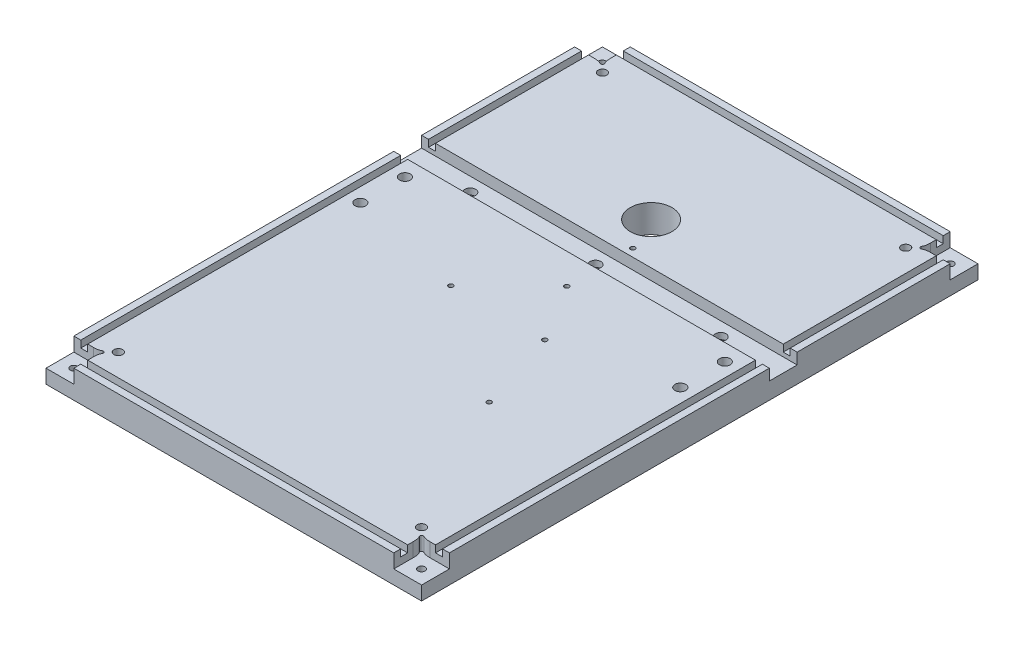
SolidWorks part; units mm, degrees
ref_plane "Front Plane" through (0, 0, 0) normal (0, 0, 1) x (1, 0, 0)
ref_plane "Top Plane" through (0, 0, 0) normal (0, 1, 0) x (1, 0, 0)
ref_plane "Right Plane" through (0, 0, 0) normal (1, 0, 0) x (0, 0, -1)
sketch "Base" plane through (0, 0, 0) normal (0, 1, 0) x (1, 0, 0)
  line L1 (-201.9764, 133.7508) -> (140.9236, 133.7508)
  line L2 (-201.9764, 133.7508) -> (-201.9764, -374.2492)
  line L3 (-201.9764, -374.2492) -> (140.9236, -374.2492)
  line L4 (140.9236, 133.7508) -> (140.9236, -374.2492)
  dimension "D1" = 342.9
  dimension "D2" = 508
extrude "Boss-Extrude1" add sketch "Base" along normal blind 25.4
sketch "Sketch2" plane through (0, 25.4, 0) normal (0, 1, 0) x (1, 0, 0)
  line L1 (172.6736, -31.3492) -> (-233.7264, -31.3492)
  line L2 (172.6736, -31.3492) -> (172.6736, -56.7492)
  line L3 (172.6736, -56.7492) -> (-233.7264, -56.7492)
  line L4 (-233.7264, -31.3492) -> (-233.7264, -56.7492)
  line L6 (140.9236, 133.7508) -> (-201.9764, 133.7508) construction
  line L9 (-30.5264, 133.7508) -> (-30.5264, -374.2492) construction
  line L10 (-201.9764, -374.2492) -> (140.9236, -374.2492) construction
  point P6 (-30.5264, -31.3492)
  dimension "D1" = 317.5
  dimension "D2" = 25.4
  dimension "D3" = 406.4
extrude "Cut-Extrude1" cut sketch "Sketch2" against normal blind 10.16
hole_wizard "CBORE for 3/8 Socket Head Cap Screw4" positions "3DSketch1" profile "Sketch3" counterbore size "3/8" standard "ANSI Inch" end condition up to next
sketch3d "3DSketch1"
  line L3 (-201.9764, 0, -133.7508) -> (-201.9764, 0, 374.2492) construction
  point P0 (83.7736, 0, 44.0492)
  point P2 (-30.5264, 0, 44.0492)
  point P4 (-144.8264, 0, 44.0492)
  dimension "D1" = 12.7
  dimension "D2" = 12.7
  dimension "D3" = 12.7
  dimension "D4" = 171.45
  dimension "D5" = 114.3
  dimension "D6" = 114.3
sketch "Sketch3" plane through (83.7736, 0, 44.0492) normal (1, 0, 0) x (0, 0, -1)
  line L0 (0, 0) -> (0, 15.24)
  line L1 (0, 15.24) -> (4.9022, 15.24)
  line L3 (4.9022, 15.24) -> (4.9022, 9.525)
  line L4 (4.9022, 9.525) -> (7.9375, 9.525)
  line L5 (7.9375, 9.525) -> (7.9375, 0)
  line L7 (7.9375, 0) -> (0, 0)
  line L11 (0, -6.35) -> (0, 107.95) construction
  dimension "Thru Hole Dia." = 9.8044
  dimension "Thru Hole Depth" = 15.24
  dimension "C'Bore Dia." = 15.875
  dimension "C'Bore Depth" = 9.525
hole_wizard "CBORE for 3/8 Socket Head Cap Screw3" positions "Sketch4" profile "Sketch6" counterbore size "3/8" standard "ANSI Inch" end condition up to next
sketch "Sketch4" plane through (0, 0, 0) normal (0, -1, 0) x (-1, 0, 0)
  line L0 (201.9764, -56.7492) -> (-140.9236, -56.7492) construction
  line L1 (-140.9236, -374.2492) -> (-140.9236, 133.7508) construction
  line L3 (201.9764, 133.7508) -> (201.9764, -374.2492) construction
  point P0 (-115.5236, -71.9892)
  point P2 (-115.5236, -112.6292)
  point P4 (176.5764, -71.9892)
  point P6 (176.5764, -112.6292)
  dimension "D1" = 15.24
  dimension "D2" = 25.4
  dimension "D3" = 25.4
  dimension "D4" = 40.64
  dimension "D5" = 15.24
  dimension "D6" = 25.4
  dimension "D7" = 40.64
  dimension "D8" = 25.4
sketch "Sketch6" plane through (115.5236, 0, 71.9892) normal (1, 0, 0) x (0, 0, -1)
  line L0 (0, 0) -> (0, 25.4)
  line L1 (0, 25.4) -> (4.9022, 25.4)
  line L3 (4.9022, 25.4) -> (4.9022, 15.24)
  line L4 (4.9022, 15.24) -> (7.9375, 15.24)
  line L5 (7.9375, 15.24) -> (7.9375, 0)
  line L7 (7.9375, 0) -> (0, 0)
  line L11 (0, -6.35) -> (0, 107.95) construction
  dimension "Thru Hole Dia." = 9.8044
  dimension "Thru Hole Depth" = 25.4
  dimension "C'Bore Dia." = 15.875
  dimension "C'Bore Depth" = 15.24
hole_wizard "CBORE for 1/4 Socket Head Cap Screw1" positions "3DSketch2" profile "Sketch9" counterbore size "1/4" standard "ANSI Inch" end condition up to next
sketch3d "3DSketch2"
  line L0 (140.9236, 0, -133.7508) -> (-201.9764, 0, -133.7508) construction
  line L1 (140.9236, 0, 374.2492) -> (140.9236, 0, -133.7508) construction
  line L2 (-201.9764, 0, -133.7508) -> (-201.9764, 0, 374.2492) construction
  line L3 (-201.9764, 0, 374.2492) -> (140.9236, 0, 374.2492) construction
  point P0 (128.2236, 0, 361.5492)
  point P2 (-189.2764, 0, 361.5492)
  point P4 (-189.2764, 0, -121.0508)
  point P6 (128.2236, 0, -121.0508)
  dimension "D1" = 12.7
  dimension "D2" = 12.7
  dimension "D3" = 12.7
  dimension "D4" = 12.7
  dimension "D5" = 12.7
  dimension "D6" = 12.7
  dimension "D7" = 12.7
  dimension "D8" = 12.7
sketch "Sketch9" plane through (128.2236, 0, 361.5492) normal (1, 0, 0) x (0, 0, -1)
  line L0 (0, 0) -> (0, 25.4)
  line L1 (0, 25.4) -> (3.2639, 25.4)
  line L3 (3.2639, 25.4) -> (3.2639, 6.35)
  line L4 (3.2639, 6.35) -> (5.5562, 6.35)
  line L5 (5.5562, 6.35) -> (5.5562, 0)
  line L7 (5.5562, 0) -> (0, 0)
  line L11 (0, -6.35) -> (0, 107.95) construction
  dimension "Thru Hole Dia." = 6.5278
  dimension "Thru Hole Depth" = 25.4
  dimension "C'Bore Dia." = 11.1125
  dimension "C'Bore Depth" = 6.35
sketch "Sketch8" plane through (0, 25.4, 0) normal (0, 1, 0) x (1, 0, 0)
  line L0 (116.3173, -347.4744) -> (115.5236, -348.8492) construction
  line L1 (140.9236, -374.2492) -> (115.5236, -374.2492)
  line L2 (140.9236, -374.2492) -> (140.9236, -348.8492)
  line L3 (140.9236, -348.8492) -> (123.1436, -348.8492)
  line L4 (115.5236, -374.2492) -> (115.5236, -356.4692)
  line L5 (-201.9764, -374.2492) -> (-176.5764, -374.2492)
  line L6 (-201.9764, -374.2492) -> (-201.9764, -348.8492)
  line L7 (-201.9764, -348.8492) -> (-184.1964, -348.8492)
  line L8 (-176.5764, -374.2492) -> (-176.5764, -356.4692)
  line L9 (-201.9764, 133.7508) -> (-176.5764, 133.7508)
  line L10 (-201.9764, 133.7508) -> (-201.9764, 108.3508)
  line L11 (-201.9764, 108.3508) -> (-184.1964, 108.3508)
  line L12 (-176.5764, 133.7508) -> (-176.5764, 115.9708)
  line L13 (140.9236, 133.7508) -> (115.5236, 133.7508)
  line L14 (140.9236, 133.7508) -> (140.9236, 108.3508)
  line L15 (140.9236, 108.3508) -> (123.1436, 108.3508)
  line L16 (115.5236, 133.7508) -> (115.5236, 115.9708)
  line L17 (115.5236, -348.8492) -> (123.1436, -348.8492) construction
  line L18 (115.5236, -356.4692) -> (115.5236, -348.8492) construction
  line L19 (115.5236, -348.8492) -> (114.1488, -349.6429) construction
  line L20 (115.5236, 108.3508) -> (116.3173, 106.976) construction
  line L21 (115.5236, 108.3508) -> (114.1488, 109.1446) construction
  line L22 (-176.5764, 108.3508) -> (-175.2016, 109.1446) construction
  line L23 (-176.5764, 108.3508) -> (-177.3702, 106.976) construction
  line L24 (-176.5764, -348.8492) -> (-175.2016, -349.6429) construction
  line L25 (-176.5764, -348.8492) -> (-177.3702, -347.4744) construction
  arc A0 (116.3173, -347.4744) -> (114.1488, -349.6429) centre (115.5236, -348.8492) ccw
  arc A1 (114.1488, 109.1446) -> (116.3173, 106.976) centre (115.5236, 108.3508) ccw
  arc A2 (-177.3702, 106.976) -> (-175.2016, 109.1446) centre (-176.5764, 108.3508) ccw
  arc A3 (-175.2016, -349.6429) -> (-177.3702, -347.4744) centre (-176.5764, -348.8492) ccw
  spline S0 degree 3 poles (123.1436, -348.8492) (120.8225, -348.8492) (118.3275, -348.6349) (116.3173, -347.4744) knots 0 0 0 0 1 1 1 1
  spline S1 degree 3 poles (115.5236, -356.4692) (115.5236, -353.9168) (115.3093, -351.6531) (114.1488, -349.6429) knots 0 0 0 0 1 1 1 1
  spline S2 degree 3 poles (123.1436, 108.3508) (120.8225, 108.3508) (118.3275, 108.1366) (116.3173, 106.976) knots 0 0 0 0 1 1 1 1
  spline S3 degree 3 poles (114.1488, 109.1446) (115.3093, 111.1547) (115.5236, 113.6497) (115.5236, 115.9708) knots 0 0 0 0 1 1 1 1
  spline S4 degree 3 poles (-176.5764, 115.9708) (-176.5764, 113.4184) (-176.3621, 111.1547) (-175.2016, 109.1446) knots 0 0 0 0 1 1 1 1
  spline S5 degree 3 poles (-177.3702, 106.976) (-179.3803, 108.1366) (-181.8753, 108.3508) (-184.1964, 108.3508) knots 0 0 0 0 1 1 1 1
  spline S6 degree 3 poles (-175.2016, -349.6429) (-176.7942, -352.4013) (-176.5764, -354.9687) (-176.5764, -356.4692) knots 0 0 0 0 1 1 1 1
  spline S7 degree 3 poles (-177.3702, -347.4744) (-180.1285, -349.0669) (-182.696, -348.8492) (-184.1964, -348.8492) knots 0 0 0 0 1 1 1 1
  point P23 (117.1111, -348.8492)
  point P27 (115.5236, -350.4367)
  dimension "D9" = 7.62
  dimension "D10" = 1.5875
  dimension "D15" = 60
  dimension "D16" = 1.5875
  dimension "D20" = 3.175
  dimension "D25" = 60
  dimension "D28" = 3.175
  dimension "D2" = 25.4
  dimension "D3" = 25.4
  dimension "D4" = 25.4
  dimension "D5" = 25.4
  dimension "D6" = 25.4
  dimension "D7" = 25.4
  dimension "D8" = 25.4
  dimension "D11" = 7.62
  dimension "D12" = 25.4
  dimension "D13" = 60
  dimension "D14" = 60
  dimension "D17" = 60
  dimension "D18" = 7.62
  dimension "D19" = 7.62
  dimension "D21" = 60
  dimension "D22" = 60
  dimension "D23" = 7.62
  dimension "D24" = 7.62
  dimension "D26" = 60
  dimension "D27" = 7.62
  dimension "D29" = 7.62
extrude "Cut-Extrude3" cut sketch "Sketch8" against normal blind 12.7
sketch "Sketch10" plane through (0, 25.4, 0) normal (0, 1, 0) x (1, 0, 0)
  line L1 (128.2236, 108.3508) -> (134.5736, 108.3508)
  line L2 (128.2236, 108.3508) -> (128.2236, -348.8492)
  line L3 (128.2236, -348.8492) -> (134.5736, -348.8492)
  line L4 (134.5736, 108.3508) -> (134.5736, -348.8492)
  line L5 (140.9236, -348.8492) -> (140.9236, -56.7492) construction
  line L8 (-201.9764, 108.3508) -> (-201.9764, -31.3492) construction
  line L9 (-195.6264, 108.3508) -> (-189.2764, 108.3508)
  line L10 (-195.6264, 108.3508) -> (-195.6264, -348.8492)
  line L11 (-195.6264, -348.8492) -> (-189.2764, -348.8492)
  line L12 (-189.2764, 108.3508) -> (-189.2764, -348.8492)
  line L13 (-184.1964, -348.8492) -> (-201.9764, -348.8492) construction
  line L14 (-201.9764, 108.3508) -> (-184.1964, 108.3508) construction
  line L15 (123.1436, 108.3508) -> (140.9236, 108.3508) construction
  line L16 (140.9236, -348.8492) -> (123.1436, -348.8492) construction
  line L17 (-176.5764, 115.9708) -> (-176.5764, 133.7508) construction
  line L18 (-176.5764, 127.4008) -> (115.5236, 127.4008)
  line L19 (-176.5764, 127.4008) -> (-176.5764, 121.0508)
  line L20 (-176.5764, 121.0508) -> (115.5236, 121.0508)
  line L21 (115.5236, 127.4008) -> (115.5236, 121.0508)
  line L22 (115.5236, 133.7508) -> (115.5236, 115.9708) construction
  line L23 (115.5236, 133.7508) -> (-176.5764, 133.7508) construction
  line L24 (-176.5764, -374.2492) -> (-176.5764, -356.4692) construction
  line L25 (-176.5764, -361.5492) -> (115.5236, -361.5492)
  line L26 (-176.5764, -361.5492) -> (-176.5764, -367.8992)
  line L27 (-176.5764, -367.8992) -> (115.5236, -367.8992)
  line L28 (115.5236, -361.5492) -> (115.5236, -367.8992)
  line L29 (115.5236, -356.4692) -> (115.5236, -374.2492) construction
  line L30 (-176.5764, -374.2492) -> (115.5236, -374.2492) construction
  dimension "D1" = 6.35
  dimension "D2" = 6.35
  dimension "D3" = 6.35
  dimension "D4" = 6.35
  dimension "D5" = 6.35
  dimension "D6" = 6.35
  dimension "D7" = 6.35
  dimension "D8" = 6.35
extrude "Cut-Extrude4" cut sketch "Sketch10" against normal blind 6.35
hole_wizard "3/8-16 Tapped Hole2" positions "Sketch17" profile "Sketch18" tap size "3/8-16" standard "ANSI Inch" end condition up to next
sketch "Sketch17" plane through (0, 0, 0) normal (0, -1, 0) x (-1, 0, 0)
  line L0 (-140.9236, 133.7508) -> (201.9764, 133.7508) construction
  line L1 (-140.9236, -374.2492) -> (-140.9236, 133.7508) construction
  line L2 (201.9764, 133.7508) -> (201.9764, -374.2492) construction
  line L3 (201.9764, -374.2492) -> (-140.9236, -374.2492) construction
  point P0 (-107.9036, -341.2292)
  point P2 (168.9564, -341.2292)
  point P4 (168.9564, 100.7308)
  point P6 (-107.9036, 100.7308)
  dimension "D1" = 33.02
  dimension "D2" = 33.02
  dimension "D3" = 33.02
  dimension "D4" = 33.02
  dimension "D5" = 33.02
  dimension "D6" = 33.02
  dimension "D7" = 33.02
  dimension "D8" = 33.02
sketch "Sketch18" plane through (107.9036, 0, 341.2292) normal (1, 0, 0) x (0, 0, -1)
  line L0 (0, 0) -> (0, 25.4)
  line L1 (0, 25.4) -> (3.9687, 25.4)
  line L2 (3.9687, 25.4) -> (3.9687, 0)
  line L5 (3.9687, 0) -> (0, 0)
  line L11 (0, -6.35) -> (0, 107.95) construction
  dimension "Thru Tap Drill Dia." = 7.9375
  dimension "Thru Tap Drill Depth" = 25.4
cosmetic thread "Hole Thread5" parameters "D2"=9.525
cosmetic thread "Hole Thread6" parameters "D2"=9.525
cosmetic thread "Hole Thread7" parameters "D2"=9.525
cosmetic thread "Hole Thread8" parameters "D2"=9.525
sketch "Sketch19" plane through (0, 0, 0) normal (0, -1, 0) x (1, 0, 0)
  circle A0 centre (-168.9564, -100.7308) radius 9.525
  circle A1 centre (-168.9564, 341.2292) radius 9.525
  circle A2 centre (107.9036, 341.2292) radius 9.525
  circle A3 centre (108.2173, -100.7308) radius 9.525
  dimension "D1" = 19.05
  dimension "D2" = 19.05
  dimension "D3" = 19.05
  dimension "D4" = 19.05
extrude "Cut-Extrude5" cut sketch "Sketch19" against normal blind 1.27
ref_plane "Plane1" through (0, 0, 120.2492) normal (0, 0, 1) x (1, 0, 0)
sketch "Sketch20" plane through (0, 0, 0) normal (0, -1, 0) x (1, 0, 0)
  line L0 (-30.5264, -133.7508) -> (-30.5264, 374.2492) construction
  line L1 (140.9236, -133.7508) -> (-201.9764, -133.7508) construction
  line L2 (-201.9764, 374.2492) -> (140.9236, 374.2492) construction
  line L3 (128.2236, 31.3492) -> (-189.2764, 31.3492) construction
  line L4 (-30.5264, 12.2992) -> (-30.5264, 36.1117) construction
  line L5 (-201.9764, 24.2054) -> (140.9236, 24.2054) construction
  line L6 (-201.9764, -133.7508) -> (-201.9764, 374.2492) construction
  line L7 (140.9236, 374.2492) -> (140.9236, -133.7508) construction
  line L8 (-148.6364, 243.5844) -> (-189.2764, 243.5844) construction
  line L9 (-148.6364, 198.2344) -> (-189.2764, 198.2344) construction
  line L10 (-148.6364, 243.5844) -> (-189.2764, 243.5844) construction
  line L11 (-148.6364, 198.2344) -> (-189.2764, 198.2344) construction
  line L16 (-15.3296, 70.4144) -> (-13.8564, 70.4144)
  line L17 (-15.3296, 88.8294) -> (-15.3296, 70.4144)
  line L18 (-125.4132, 88.8294) -> (-15.3296, 88.8294)
  line L19 (-125.4132, 70.4144) -> (-125.4132, 88.8294)
  line L20 (-126.8864, 70.4144) -> (-125.4132, 70.4144)
  line L21 (-126.8864, 283.7744) -> (-126.8864, 70.4144)
  line L22 (-13.8564, 283.7744) -> (-126.8864, 283.7744)
  line L23 (-13.8564, 70.4144) -> (-13.8564, 283.7744)
  line L24 (-15.3296, 70.4144) -> (-13.8564, 70.4144) construction
  line L25 (-15.3296, 88.8294) -> (-15.3296, 70.4144) construction
  line L26 (-125.4132, 88.8294) -> (-15.3296, 88.8294) construction
  line L27 (-125.4132, 70.4144) -> (-125.4132, 88.8294) construction
  line L28 (-126.8864, 70.4144) -> (-125.4132, 70.4144) construction
  line L29 (-126.8864, 283.7744) -> (-126.8864, 70.4144) construction
  line L30 (-13.8564, 283.7744) -> (-126.8864, 283.7744) construction
  line L31 (-13.8564, 70.4144) -> (-13.8564, 283.7744) construction
  line L32 (107.7004, 70.4144) -> (109.1736, 70.4144)
  line L33 (107.7004, 88.8294) -> (107.7004, 70.4144)
  line L34 (-2.3832, 88.8294) -> (107.7004, 88.8294)
  line L35 (-2.3832, 70.4144) -> (-2.3832, 88.8294)
  line L36 (-3.8564, 70.4144) -> (-2.3832, 70.4144)
  line L37 (-3.8564, 283.7744) -> (-3.8564, 70.4144)
  line L38 (109.1736, 283.7744) -> (-3.8564, 283.7744)
  line L39 (109.1736, 70.4144) -> (109.1736, 283.7744)
  line L40 (107.7004, 70.4144) -> (109.1736, 70.4144) construction
  line L41 (107.7004, 88.8294) -> (107.7004, 70.4144) construction
  line L42 (-2.3832, 88.8294) -> (107.7004, 88.8294) construction
  line L43 (-2.3832, 70.4144) -> (-2.3832, 88.8294) construction
  line L44 (-3.8564, 70.4144) -> (-2.3832, 70.4144) construction
  line L45 (-3.8564, 283.7744) -> (-3.8564, 70.4144) construction
  line L46 (109.1736, 283.7744) -> (-3.8564, 283.7744) construction
  line L47 (109.1736, 70.4144) -> (109.1736, 283.7744) construction
  line L172 (109.1736, 126.9294) -> (-126.4579, 126.9294) construction
  line L216 (39.8684, 206.6921) -> (54.1559, 206.6921)
  line L217 (-201.9764, 374.2492) -> (-201.9764, -133.7508)
  line L218 (-201.9764, -133.7508) -> (140.9236, -133.7508)
  line L219 (140.9236, -133.7508) -> (140.9236, 374.2492)
  line L220 (140.9236, 374.2492) -> (-201.9764, 374.2492)
  line L221 (-201.9764, 374.2492) -> (-201.9764, -133.7508) construction
  line L222 (-201.9764, -133.7508) -> (140.9236, -133.7508) construction
  line L223 (140.9236, -133.7508) -> (140.9236, 374.2492) construction
  line L224 (140.9236, 374.2492) -> (-201.9764, 374.2492) construction
  line L225 (54.1559, 206.6921) -> (54.1559, 216.2171)
  line L226 (54.1559, 216.2171) -> (39.8684, 216.2171)
  line L227 (39.8684, 206.6921) -> (54.1559, 206.6921) construction
  line L228 (54.1559, 206.6921) -> (54.1559, 216.2171) construction
  line L229 (54.1559, 216.2171) -> (39.8684, 216.2171) construction
  circle A0 centre (115.5236, 310.7492) radius 3.175 construction
  circle A1 centre (64.7236, 310.7492) radius 3.175 construction
  circle A2 centre (115.5236, 310.7492) radius 3.175 construction
  circle A3 centre (64.7236, 310.7492) radius 3.175 construction
  circle A4 centre (64.7236, -70.2508) radius 3.175 construction
  circle A5 centre (115.5236, -70.2508) radius 3.175 construction
  circle A6 centre (64.7236, -70.2508) radius 3.175 construction
  circle A7 centre (115.5236, -70.2508) radius 3.175 construction
  circle A8 centre (-30.5264, -6.7508) radius 19.05
  circle A9 centre (-30.5264, 44.0492) radius 7.9375 construction
  circle A10 centre (-30.5264, 44.0492) radius 7.9375 construction
  circle A13 centre (-16.2389, 84.5304) radius 2.0955 construction
  circle A14 centre (-16.2389, 84.5304) radius 2.0955
  circle A15 centre (-16.2389, 24.2054) radius 2.0955 construction
  circle A16 centre (-16.2389, 24.2054) radius 2.0955
  arc A18 (39.8684, 216.2171) -> (39.8684, 206.6921) centre (39.8684, 211.4546) ccw
  arc A19 (39.8684, 216.2171) -> (39.8684, 206.6921) centre (39.8684, 211.4546) ccw construction
  circle A23 centre (39.8684, 211.4546) radius 2.0955 construction
  circle A24 centre (16.0559, 136.9179) radius 2.0955 construction
  circle A25 centre (-69.6691, 136.9179) radius 2.0955 construction
  circle A26 centre (39.8684, 211.4546) radius 2.0955
  circle A27 centre (16.0559, 136.9179) radius 2.0955
  circle A28 centre (-69.6691, 136.9179) radius 2.0955
  point P33 (-30.5264, 24.2054)
  dimension "D1" = 38.1
  dimension "D2" = 38.1
  dimension "D5" = 38.1
  dimension "D3" = 0
  dimension "D4" = 0
  dimension "D8" = 0
  dimension "D9" = 0
extrude "Cut-Extrude6" cut sketch "Sketch20" against normal through all
ref_plane "Plane2" through (-30.5264, 0, 0) normal (1, 0, 0) x (0, 0, -1)
ref_plane "Plane3" through (0, 0, 24.2054) normal (0, 0, -1) x (-1, 0, 0)
